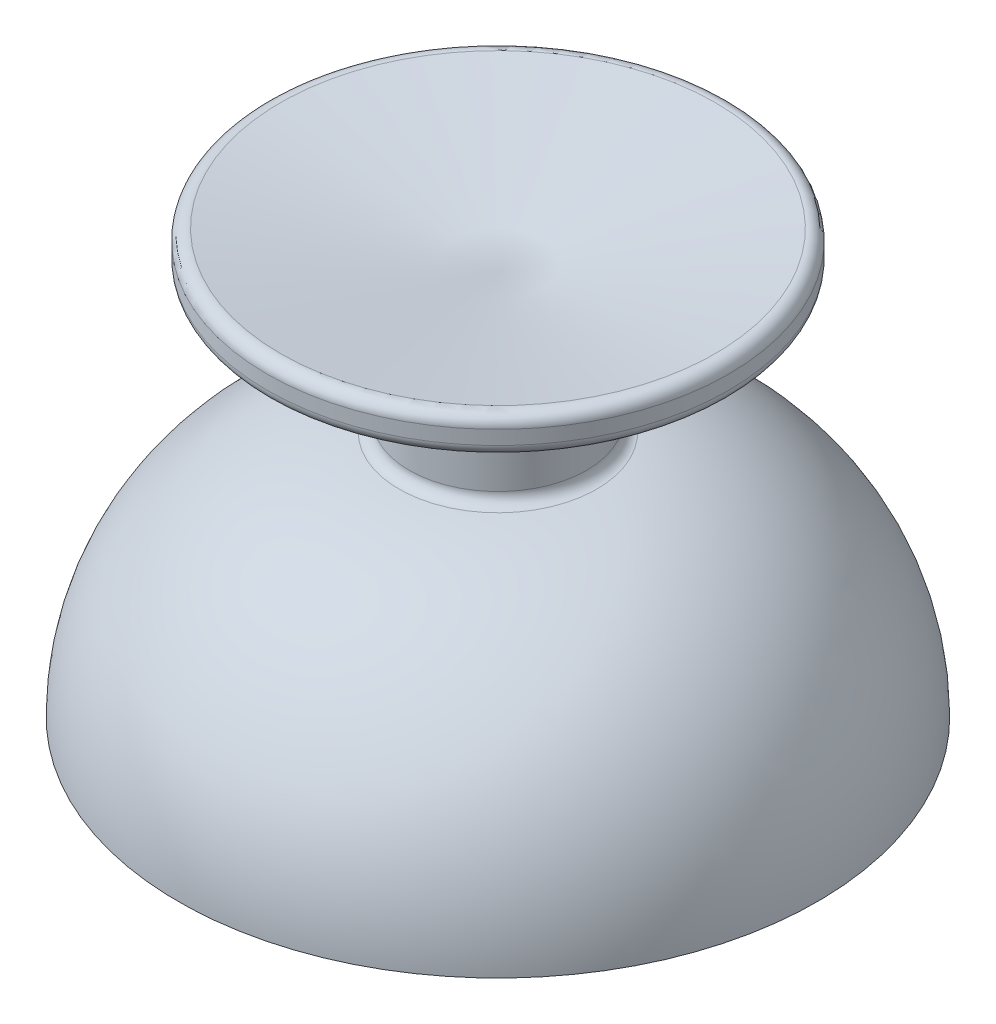
SolidWorks part; units mm, degrees
ref_plane "Front Plane" through (0, 0, 0) normal (0, 0, 1) x (1, 0, 0)
ref_plane "Top Plane" through (0, 0, 0) normal (0, 1, 0) x (1, 0, 0)
ref_plane "Right Plane" through (0, 0, 0) normal (1, 0, 0) x (0, 0, -1)
sketch "Sketch1" plane through (0, 0, 0) normal (0, 0, 1) x (1, 0, 0)
  line L0 (0, 0) -> (0, 66.0903) construction
  line L1 (0, -55) -> (0, 55) construction
  line L2 (55, 0) -> (-55, 0) construction
  line L3 (-3.175, 11.1125) -> (39.3975, 11.1125) construction
  line L4 (-14.2875, 0) -> (-14.2875, 40.0379) construction
  line L5 (-3.175, 11.1125) -> (0, 11.1125)
  line L6 (-3.175, 10.3505) -> (0, 10.3505)
  line L7 (0, 10.3505) -> (0, 11.1125)
  line L8 (-13.5255, 0) -> (-14.2875, 0)
  arc A0 (-14.2875, 0) -> (-3.175, 11.1125) centre (-3.175, 0) cw
  arc A1 (-13.5255, 0) -> (-3.175, 10.3505) centre (-3.175, 0) cw
  dimension "D1" = 28.575
  dimension "D2" = 11.1125
  dimension "D3" = 0.762
revolve "Revolve1" add sketch "Sketch1" angle 360 about L0
sketch "Sketch2" plane through (0, 0, 0) normal (0, 0, 1) x (1, 0, 0)
  line L0 (0, 11.1125) -> (0, 74.753) construction
  line L1 (3.175, 11.1125) -> (-3.175, 11.1125) construction
  line L2 (0, -6.1119) -> (0, 6.1119) construction
  line L3 (0, 11.1125) -> (-3.9688, 10.9739)
  line L4 (-3.9688, 10.9739) -> (-3.9688, 13.8598)
  line L5 (-3.9688, 13.8598) -> (-10.3188, 17.526)
  line L6 (-10.3188, 17.526) -> (-10.3188, 19.05)
  line L7 (-10.3188, 19.05) -> (0, 17.2305)
  line L8 (0, 17.2305) -> (0, 11.1125)
  line L9 (15.7163, 0) -> (-15.7163, 0) construction
  dimension "D2" = 19.05
  dimension "D3" = 20.6375
  dimension "D4" = 7.9375
  dimension "D5" = 100
  dimension "D6" = 60
  dimension "D7" = 1.524
  dimension "D8" = 92
revolve "Revolve2" add sketch "Sketch2" angle 360 about L0
sketch "Sketch3" plane through (0, 10.3505, 0) normal (0, -1, 0) x (1, 0, 0)
  circle A0 centre (0, 0) radius 2.54
  dimension "D1" = 5.08
extrude "Boss-Extrude1" add sketch "Sketch3" along normal offset from surface (7.1755 mm away) 3.175 up to face at (0, 0, -13.5255)
fillet "Fillet1" radius 2.54 1 edges at (0, 10.3505, 2.54)
sketch "Sketch5" plane through (0, 3.175, 0) normal (0, -1, 0) x (1, 0, 0)
  circle A0 centre (0, 0) radius 2
  dimension "D1" = 4
extrude "Cut-Extrude1" cut sketch "Sketch5" against normal blind 9.525
sketch "Sketch6" plane through (0, 3.175, 0) normal (0, -1, 0) x (1, 0, 0)
  line L0 (0, 0) -> (0, 20.2417) construction
  line L1 (0, -6.1119) -> (0, 6.1119) construction
  line L2 (-1.5, 1.3229) -> (-1.5, -1.3229)
  line L3 (1.5, 1.3229) -> (1.5, -1.3229)
  circle A0 centre (0, 0) radius 2 construction
  arc A1 (-1.5, -1.3229) -> (-1.5, 1.3229) centre (0, 0) cw
  arc A2 (1.5, -1.3229) -> (1.5, 1.3229) centre (0, 0) ccw
  dimension "D1" = 3
extrude "Boss-Extrude2" add sketch "Sketch6" against normal up to surface (9.525 mm away) up to face at (0, 12.7, -2)
ref_axis "Axis3" through (0, 0, 15.7163) along (0, 0, -1)
ref_plane "Plane2" through (0, 0, 0) normal (0.9063, -0.4226, 0) x (0, 0, -1)
ref_plane "Plane3" through (0, 0, 0) normal (-0.4226, -0.9063, 0) x (0.9063, -0.4226, 0)
fillet "Fillet2" radius 0.508 1 edges at (0, 13.8598, -3.9688)
fillet "Fillet3" radius 0.508 2 edges at (0, 19.05, -10.3188) (0, 17.526, -10.3188)
fillet "Fillet5" radius 0.508 1 edges at (0, 11.0841, -3.9688)
